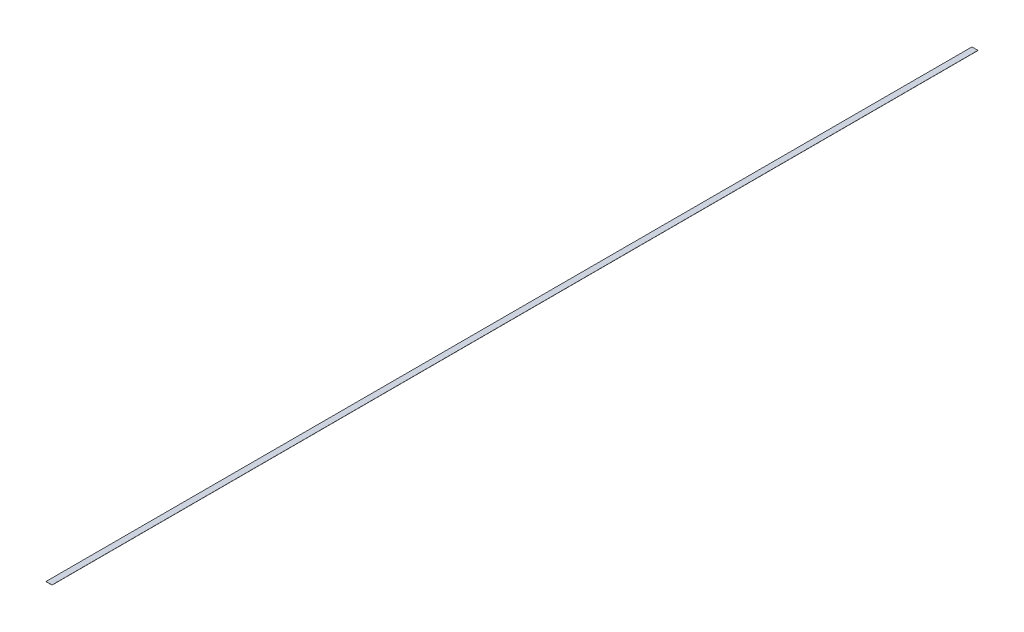
SolidWorks part; units mm, degrees
ref_plane "Front Plane" through (0, 0, 0) normal (0, 0, 1) x (1, 0, 0)
ref_plane "Top Plane" through (0, 0, 0) normal (0, 1, 0) x (1, 0, 0)
ref_plane "Right Plane" through (0, 0, 0) normal (1, 0, 0) x (0, 0, -1)
sketch "Sketch1" plane through (0, 0, 0) normal (0, 1, 0) x (1, 0, 0)
  line L0 (-25.4, 3429) -> (25.4, 3469.1482)
  line L1 (-25.4, -3886.2) -> (25.4, -3886.2)
  line L2 (-25.4, -3886.2) -> (-25.4, 3886.2)
  line L3 (-25.4, 3886.2) -> (25.4, 3886.2)
  line L4 (25.4, -3886.2) -> (25.4, 3886.2)
  line L5 (-25.4, -3886.2) -> (25.4, 3886.2) construction
  line L6 (-25.4, 3886.2) -> (25.4, -3886.2) construction
  point P0 (0, 0)
  dimension "D1" = 50.8
  dimension "D2" = 7772.4
  dimension "D3" = 141.68
  dimension "D4" = 457.2
extrude "Boss-Extrude1" add sketch "Sketch1" along normal blind 1.27 contours L1 L4 L0 L2 | L2 L1 L4 L3 region at (0.0232, 0, 218.5538)
